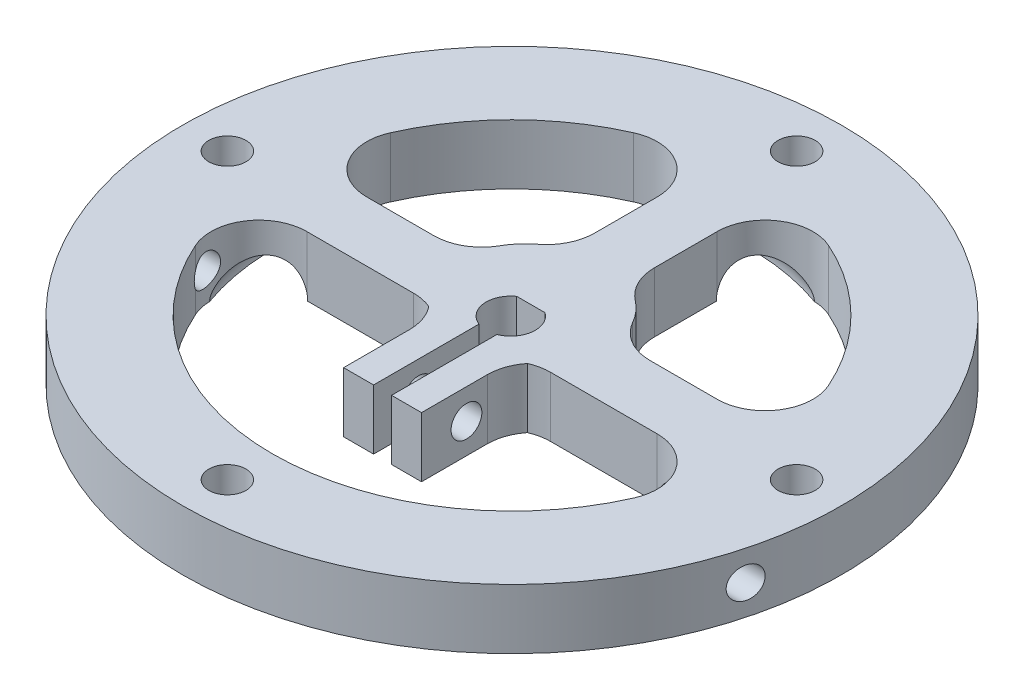
SolidWorks part; units mm, degrees
ref_plane "Front Plane" through (0, 0, 0) normal (0, 0, 1) x (1, 0, 0)
ref_plane "Top Plane" through (0, 0, 0) normal (0, 1, 0) x (1, 0, 0)
ref_plane "Right Plane" through (0, 0, 0) normal (1, 0, 0) x (0, 0, -1)
ref_plane "Plane1" through (0, 46.35, 0) normal (0, 1, 0) x (1, 0, 0)
sketch "Sketch1" plane through (0, 46.35, 0) normal (0, 1, 0) x (1, 0, 0)
  line L0 (-4.1275, -4.191) -> (-4.1275, -13.716)
  line L3 (-1.5, 2) -> (1.5, 2) construction
  line L4 (-1.5, 2) -> (1.5, 2)
  line L5 (0, -0.127) -> (0, -30.1625) construction
  line L6 (4.1275, -8.9535) -> (-4.1275, -8.9535) construction
  line L7 (-4.1275, -13.716) -> (-0.9525, -13.716)
  line L8 (-0.9525, -13.716) -> (-0.9525, -2.5492)
  line L10 (4.1275, -13.716) -> (0.9525, -13.716)
  line L11 (0.9525, -13.716) -> (0.9525, -2.5492)
  line L12 (4.1275, -13.716) -> (4.1275, -4.191)
  line L13 (0, 0) -> (0, 30.1625) construction
  line L14 (0, 0) -> (-30.1625, 0) construction
  line L15 (0, 0) -> (30.1625, 0) construction
  line L16 (-3.175, 8.9803) -> (-3.175, 25.2008)
  line L17 (3.175, 8.9803) -> (3.175, 25.2008)
  line L18 (-7.9108, 3.175) -> (-25.2008, 3.175)
  line L19 (-5.5875, -3.175) -> (-25.2008, -3.175)
  line L20 (5.5875, -3.175) -> (25.2008, -3.175)
  line L21 (7.9108, 3.175) -> (25.2008, 3.175)
  arc A0 (-4.1275, -4.191) -> (-3.175, 8.9803) centre (-0.773, 2.1865) cw
  arc A3 (-1.5, 2) -> (1.5, 2) centre (0, -0.127) ccw
  arc A4 (-1.5, 2) -> (1.5, 2) centre (0, 0) ccw construction
  arc A5 (-1.5, 2) -> (1.5, 2) centre (0, 0) ccw
  arc A6 (4.1275, -4.191) -> (5.5875, -3.175) centre (0.773, 2.1865) ccw
  arc A7 (3.175, 8.9803) -> (-3.175, 8.9803) centre (0, 0) ccw
  arc A9 (-25.2008, -3.175) -> (25.2008, -3.175) centre (0, 0) ccw
  circle A10 centre (0, 0) radius 30.1625 construction
  circle A11 centre (0, 0) radius 34.925
  circle A12 centre (-30.1625, 0) radius 1.9685
  circle A13 centre (0, 30.1625) radius 1.9685
  circle A14 centre (30.1625, 0) radius 1.9685
  circle A15 centre (0, -30.1625) radius 1.9685
  arc A16 (-3.175, 25.2008) -> (-25.2008, 3.175) centre (0, 0) ccw
  arc A17 (7.9108, 3.175) -> (3.175, 8.9803) centre (0.773, 2.1865) ccw
  arc A18 (25.2008, 3.175) -> (3.175, 25.2008) centre (0, 0) ccw
  point P49 (0, 0)
  dimension "D4" = 9.525
  dimension "D6" = 6.35
  dimension "D10" = 69.85
  dimension "D11" = 9.525
  dimension "D12" = 4.7625
  dimension "D13" = 3.937
  dimension "D1" = 0.127
  dimension "D2" = 1.905
  dimension "D3" = 9.525
  dimension "D5" = 3.175
  dimension "D7" = 6.35
  dimension "D8" = 6.35
  dimension "D9" = 1.016
  dimension "D14" = 4
extrude "Boss-Extrude1" add sketch "Sketch1" along normal blind 6.35 contours A7 L7 L8 A3 L4 L11 L10 region at (-33.9372, 46.35, 0)
sketch "Sketch2" plane through (-4.1275, 0, 0) normal (-1, 0, 0) x (0, 0, 1)
  line L0 (13.716, 52.7) -> (4.191, 46.35) construction
  circle A0 centre (8.9535, 49.525) radius 1.6319
  dimension "D1" = 3.2639
extrude "Cut-Extrude1" cut sketch "Sketch2" against normal through all both and the other way through all
fillet "Fillet1" radius 5.08 14 edges at (25.2008, 49.525, 3.175) (5.5875, 49.525, 3.175) (4.1275, 49.525, 4.191) (-4.1275, 49.525, 4.191) (-5.5875, 49.525, 3.175) (7.9108, 49.525, -3.175) (25.2008, 49.525, -3.175) (3.175, 49.525, -25.2008) (3.175, 49.525, -8.9803) (-3.175, 49.525, -25.2008) (-25.2008, 49.525, -3.175) (-7.9108, 49.525, -3.175) (-3.175, 49.525, -8.9803) (-25.2008, 49.525, 3.175)
sketch "Sketch3" plane through (0, 0, 0) normal (1, 0, 0) x (0, 0, -1)
  line L1 (11.9314, 46.35) -> (18.5676, 46.35) construction
  line L2 (0, 46.35) -> (21.9202, 46.35) construction
  line L3 (-34.925, 46.35) -> (34.925, 46.35) construction
  line L4 (25.0952, 46.35) -> (18.7452, 46.35)
  arc A0 (25.0952, 46.35) -> (18.7452, 46.35) centre (21.9202, 46.35) ccw
  dimension "D1" = 6.35
  dimension "D2" = 21.9202
ref_axis "Axis1" through (0, 52.7, 0) along (0, -1, 0)
revolve "Cut-Revolve1" cut sketch "Sketch3" angle 360 about axis through (0, 52.7, 0) along (0, -1, 0)
